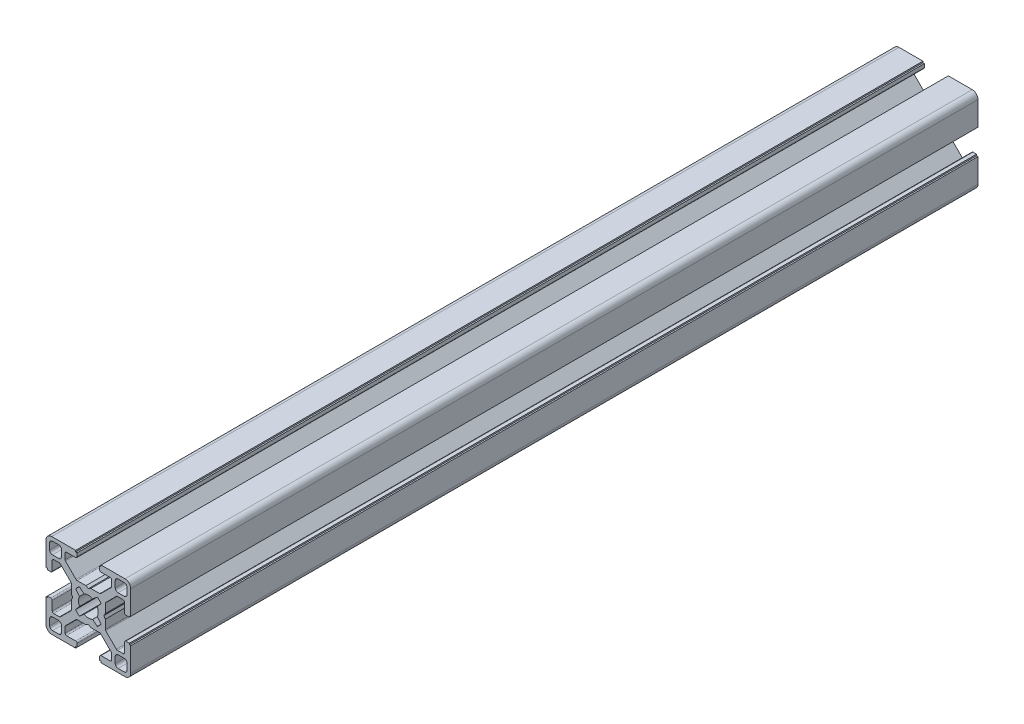
SolidWorks part; units mm, degrees
ref_plane "Front Plane" through (0, 0, 0) normal (0, 0, 1) x (1, 0, 0)
ref_plane "Top Plane" through (0, 0, 0) normal (0, 1, 0) x (1, 0, 0)
ref_plane "Right Plane" through (0, 0, 0) normal (1, 0, 0) x (0, 0, -1)
sketch "Sketch1" plane through (0, 0, 0) normal (0, 0, 1) x (1, 0, 0)
  line L0 (-15, 0) -> (15, 0) construction
  line L1 (0, -15) -> (0, 15) construction
  line L2 (-4.5, 15) -> (4.5, 15) construction
  line L3 (-4, -15) -> (4, -15) construction
  line L4 (-4.5, 15) -> (-4.5, 14.5)
  line L5 (-4.5, 14.5) -> (-4, 14.5)
  line L6 (-4, 14.5) -> (-4, 13.29)
  line L7 (-4.5, 12.79) -> (-7.7675, 12.79)
  line L8 (-8.2675, 12.29) -> (-8.2675, 10.2707)
  line L9 (-8.1211, 9.9171) -> (-4.3504, 6.1464)
  line L10 (-3.9968, 6) -> (0, 6)
  line L11 (0, 0) -> (-15, 15) construction
  line L12 (-4.5, 15) -> (-12.968, 15)
  line L14 (-12.705, 9.5135) -> (-10.5135, 9.5135)
  line L15 (-13.705, 10.5135) -> (-13.705, 12.705)
  line L16 (-12.705, 13.705) -> (-10.5135, 13.705)
  line L17 (-9.5135, 10.5135) -> (-9.5135, 12.705)
  line L18 (-13.705, 9.5135) -> (-9.5135, 13.705) construction
  line L19 (-13.705, 13.705) -> (-9.5135, 9.5135) construction
  line L20 (-3.1568, 4.5038) -> (-1.5303, 3.1477) construction
  line L21 (-4.5038, 3.1568) -> (-3.1477, 1.5303) construction
  line L22 (-6, 3.9968) -> (-6, 0)
  line L23 (-9.9171, 8.1211) -> (-6.1464, 4.3504)
  line L24 (-15, 4.5) -> (-15, 12.968)
  line L25 (-12.29, 8.2675) -> (-10.2707, 8.2675)
  line L26 (-12.79, 4.5) -> (-12.79, 7.7675)
  line L27 (-14.5, 4) -> (-13.29, 4)
  line L28 (-14.5, 4.5) -> (-14.5, 4)
  line L29 (-15, 4.5) -> (-14.5, 4.5)
  circle A0 centre (0, 0) radius 3.5
  arc A1 (-12.968, 15) -> (-15, 12.968) centre (-12.968, 12.968) ccw
  circle A2 centre (0, 0) radius 5.5 construction
  arc A3 (-10.5135, 9.5135) -> (-9.5135, 10.5135) centre (-10.5135, 10.5135) ccw
  arc A4 (-13.705, 12.705) -> (-12.705, 13.705) centre (-12.705, 12.705) cw
  arc A5 (-10.5135, 13.705) -> (-9.5135, 12.705) centre (-10.5135, 12.705) cw
  arc A6 (-12.705, 9.5135) -> (-13.705, 10.5135) centre (-12.705, 10.5135) cw
  arc A7 (-12.79, 4.5) -> (-13.29, 4) centre (-13.29, 4.5) cw
  arc A8 (-12.29, 8.2675) -> (-12.79, 7.7675) centre (-12.29, 7.7675) ccw
  arc A9 (-9.9171, 8.1211) -> (-10.2707, 8.2675) centre (-10.2707, 7.7675) ccw
  arc A10 (-6, 3.9968) -> (-6.1464, 4.3504) centre (-6.5, 3.9968) ccw
  arc A11 (-4.3504, 6.1464) -> (-3.9968, 6) centre (-3.9968, 6.5) ccw
  arc A12 (-4, 13.29) -> (-4.5, 12.79) centre (-4.5, 13.29) cw
  arc A13 (-7.7675, 12.79) -> (-8.2675, 12.29) centre (-7.7675, 12.29) ccw
  arc A14 (-8.2675, 10.2707) -> (-8.1211, 9.9171) centre (-7.7675, 10.2707) ccw
  point P4 (0, 0)
  point P8 (0, 0)
  point P13 (0, 15)
  point P15 (0, -15)
  point P16 (0, 6)
  point P23 (-11.6092, 11.6093)
  point P26 (0, 6)
  point P62 (-12.79, 4)
  point P65 (-12.79, 8.2675)
  point P68 (-10.0636, 8.2675)
  point P71 (-6, 4.2039)
  point P74 (-4.2039, 6)
  point P77 (-4, 12.79)
  point P80 (-8.2675, 12.79)
  point P83 (-8.2675, 10.0636)
  dimension "Center Hole Diameter" = 7
  dimension "D11" = 2.032
  dimension "D9" = 11
  dimension "D13" = 1
  dimension "D14" = 0.5
  dimension "Rail Height" = 30
  dimension "Rail Width" = 30
  dimension "T-Slot Width" = 8
  dimension "T-Slot Depth" = 9
  dimension "D1" = 9
  dimension "D2" = 45
  dimension "D3" = 8
  dimension "D4" = 2.21
  dimension "D5" = 16.535
  dimension "D7" = 2.54
  dimension "D6" = 1.295
  dimension "D8" = 1.246
  dimension "D10" = 10.36
  dimension "D12" = 1.905
sketch "Sketch2" plane through (0, 0, 0) normal (1, 0, 0) x (0, 0, -1)
  line L0 (-76.2, 0) -> (76.2, 0) construction
  line L2 (0, -15) -> (0, 15) construction
  line L3 (0, -15) -> (0, 15) construction
  line L4 (-76.2, -15) -> (-76.2, 15) construction
  line L5 (76.2, -15) -> (76.2, 15) construction
  point P0 (-38.7, 0)
  point P3 (0, 0)
  point P4 (38.7, 0)
  point P12 (-76.2, 0)
  point P14 (76.2, 0)
  dimension "Length" = 152.4
  dimension "D1" = 37.5
sketch "Sketch3" plane through (0, 0, 0) normal (0, 0, 1) x (1, 0, 0)
  line L0 (-4.5038, 3.1568) -> (-3.1477, 1.5303)
  line L1 (0, 3.5) -> (0, 5.5)
  line L2 (-5.5, 0) -> (-3.5, 0)
  line L7 (-6, 3.9968) -> (-6, 0) construction
  line L31 (-9.9171, 8.1211) -> (-6.1464, 4.3504) construction
  line L117 (-12.29, 8.2675) -> (-10.2707, 8.2675) construction
  line L118 (-12.79, 4.5) -> (-12.79, 7.7675) construction
  line L157 (-12.705, 9.5135) -> (-10.5135, 9.5135)
  line L158 (-9.5135, 10.5135) -> (-9.5135, 12.705)
  line L163 (-10.5135, 13.705) -> (-12.705, 13.705)
  line L164 (-13.705, 12.705) -> (-13.705, 10.5135)
  line L165 (-12.705, 9.5135) -> (-10.5135, 9.5135)
  line L166 (-9.5135, 10.5135) -> (-9.5135, 12.705)
  line L167 (-10.5135, 13.705) -> (-12.705, 13.705)
  line L168 (-13.705, 12.705) -> (-13.705, 10.5135)
  line L169 (-14.5, 4) -> (-13.29, 4) construction
  line L170 (-14.5, 4.5) -> (-14.5, 4) construction
  line L171 (-15, 4.5) -> (-14.5, 4.5) construction
  line L172 (-15, 4.5) -> (-15, 12.968) construction
  line L173 (-4.5, 15) -> (-12.968, 15) construction
  line L174 (-4.5, 15) -> (-4.5, 14.5) construction
  line L175 (-4.5, 14.5) -> (-4, 14.5) construction
  line L176 (-4, 14.5) -> (-4, 13.29) construction
  line L177 (-4.5, 12.79) -> (-7.7675, 12.79) construction
  line L178 (-8.2675, 12.29) -> (-8.2675, 10.2707) construction
  line L179 (-8.1211, 9.9171) -> (-4.3504, 6.1464) construction
  line L180 (-3.9968, 6) -> (0, 6) construction
  line L181 (-6, 3.9968) -> (-6, 0.866)
  line L182 (-9.9171, 8.1211) -> (-6.1464, 4.3504)
  line L183 (-12.29, 8.2675) -> (-10.2707, 8.2675)
  line L184 (-12.79, 4.5) -> (-12.79, 7.7675)
  line L185 (-14.5, 4) -> (-13.29, 4)
  line L186 (-14.5, 4.5) -> (-14.5, 4)
  line L187 (-15, 4.5) -> (-14.5, 4.5)
  line L188 (-15, 4.5) -> (-15, 12.968)
  line L189 (-4.5, 15) -> (-12.968, 15)
  line L190 (-4.5, 15) -> (-4.5, 14.5)
  line L191 (-4.5, 14.5) -> (-4, 14.5)
  line L192 (-4, 14.5) -> (-4, 13.29)
  line L193 (-4.5, 12.79) -> (-7.7675, 12.79)
  line L194 (-8.2675, 12.29) -> (-8.2675, 10.2707)
  line L195 (-8.1211, 9.9171) -> (-4.3504, 6.1464)
  line L196 (-3.9968, 6) -> (-0.866, 6)
  line L197 (-0.866, 6) -> (0, 5.5)
  line L198 (0, -15) -> (0, 15) construction
  line L199 (0, 0) -> (-15, 15) construction
  line L200 (0, 0) -> (-15, 15) construction
  line L201 (-3.1568, 4.5038) -> (-1.5303, 3.1477) construction
  line L202 (-3.1568, 4.5038) -> (-1.5303, 3.1477)
  line L203 (-6, 0.866) -> (-5.5, 0)
  line L204 (-15, 0) -> (15, 0) construction
  line L205 (-15, 0) -> (15, 0) construction
  line L206 (0, -15) -> (0, 15) construction
  arc A0 (-3.5, 0) -> (-3.1477, 1.5303) centre (0, 0) cw
  arc A10 (-6, 3.9968) -> (-6.1464, 4.3504) centre (-6.5, 3.9968) ccw construction
  circle A16 centre (0, 0) radius 3.5
  arc A18 (0, 3.5) -> (-1.5303, 3.1477) centre (0, 0) ccw
  arc A20 (-9.9171, 8.1211) -> (-10.2707, 8.2675) centre (-10.2707, 7.7675) ccw construction
  arc A22 (-12.29, 8.2675) -> (-12.79, 7.7675) centre (-12.29, 7.7675) ccw construction
  arc A28 (-13.29, 4) -> (-12.79, 4.5) centre (-13.29, 4.5) ccw construction
  arc A29 (-10.5135, 9.5135) -> (-9.5135, 10.5135) centre (-10.5135, 10.5135) ccw
  arc A30 (-9.5135, 12.705) -> (-10.5135, 13.705) centre (-10.5135, 12.705) ccw
  arc A31 (-12.705, 13.705) -> (-13.705, 12.705) centre (-12.705, 12.705) ccw
  arc A32 (-13.705, 10.5135) -> (-12.705, 9.5135) centre (-12.705, 10.5135) ccw
  arc A33 (-10.5135, 9.5135) -> (-9.5135, 10.5135) centre (-10.5135, 10.5135) ccw
  arc A34 (-9.5135, 12.705) -> (-10.5135, 13.705) centre (-10.5135, 12.705) ccw
  arc A35 (-12.705, 13.705) -> (-13.705, 12.705) centre (-12.705, 12.705) ccw
  arc A36 (-13.705, 10.5135) -> (-12.705, 9.5135) centre (-12.705, 10.5135) ccw
  arc A37 (-12.968, 15) -> (-15, 12.968) centre (-12.968, 12.968) ccw construction
  arc A38 (-4.5, 12.79) -> (-4, 13.29) centre (-4.5, 13.29) ccw construction
  arc A39 (-7.7675, 12.79) -> (-8.2675, 12.29) centre (-7.7675, 12.29) ccw construction
  arc A40 (-8.2675, 10.2707) -> (-8.1211, 9.9171) centre (-7.7675, 10.2707) ccw construction
  arc A41 (-4.3504, 6.1464) -> (-3.9968, 6) centre (-3.9968, 6.5) ccw construction
  arc A42 (-6, 3.9968) -> (-6.1464, 4.3504) centre (-6.5, 3.9968) ccw
  arc A43 (-9.9171, 8.1211) -> (-10.2707, 8.2675) centre (-10.2707, 7.7675) ccw
  arc A44 (-12.29, 8.2675) -> (-12.79, 7.7675) centre (-12.29, 7.7675) ccw
  arc A45 (-13.29, 4) -> (-12.79, 4.5) centre (-13.29, 4.5) ccw
  arc A46 (-12.968, 15) -> (-15, 12.968) centre (-12.968, 12.968) ccw
  arc A47 (-4.5, 12.79) -> (-4, 13.29) centre (-4.5, 13.29) ccw
  arc A48 (-7.7675, 12.79) -> (-8.2675, 12.29) centre (-7.7675, 12.29) ccw
  arc A49 (-8.2675, 10.2707) -> (-8.1211, 9.9171) centre (-7.7675, 10.2707) ccw
  arc A50 (-4.3504, 6.1464) -> (-3.9968, 6) centre (-3.9968, 6.5) ccw
  circle A51 centre (0, 0) radius 5.5 construction
  arc A52 (-3.1568, 4.5038) -> (-4.5038, 3.1568) centre (0, 0) ccw
  dimension "D3" = 60
  dimension "D4" = 60
  dimension "D1" = 0
  dimension "D2" = 0
extrude "Boss-Extrude1" add sketch "Sketch3" along normal mid plane 300
pattern_circular "CirPattern1" count 4 over 360 about axis through (0, 0, 76.2) along (0, 0, -1) of "Boss-Extrude1"
ref_plane "Contact Plane1" through (15, 0, 0) normal (1, 0, 0) x (0, 0, -1)
ref_plane "Contact Plane2" through (0, -15, 0) normal (0, 1, 0) x (1, 0, 0)
ref_plane "Contact Plane3" through (-15, 0, 0) normal (1, 0, 0) x (0, 0, -1)
ref_plane "Contact Plane4" through (0, 15, 0) normal (0, 1, 0) x (1, 0, 0)
equation "\"D1@Sketch2\" = \"Rail Height@Sketch1\" * 1.25"
equation "\"D1@Sketch1\"=\"T-Slot Width@Sketch1\"+1mm"
equation "\"D3@Sketch1\"= \"T-Slot Width@Sketch1\""
equation "\"D1@Boss-Extrude1\"=\"Length\""
equation "\"Length\" = 300"
